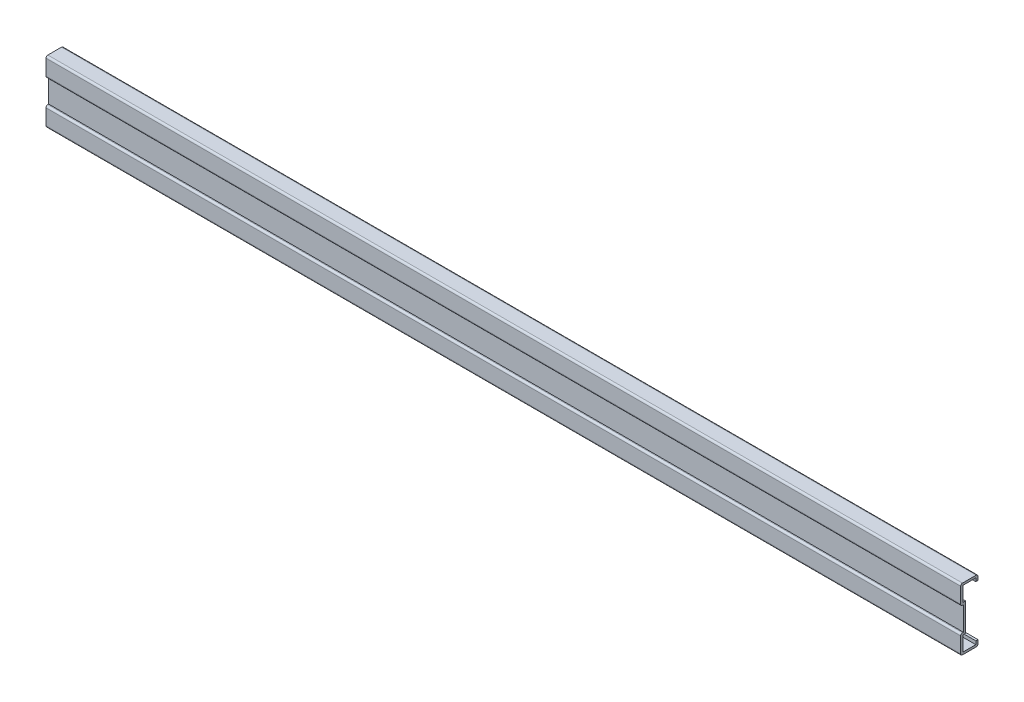
SolidWorks part; units mm, degrees
ref_plane "Спереди" through (0, 0, 0) normal (0, 0, 1) x (1, 0, 0)
ref_plane "Сверху" through (0, 0, 0) normal (0, 1, 0) x (1, 0, 0)
ref_plane "Справа" through (0, 0, 0) normal (1, 0, 0) x (0, 0, -1)
sketch "Эскиз1" plane through (0, 0, 0) normal (1, 0, 0) x (0, 0, -1)
  line L0 (0, 6.5) -> (0, -6.5)
  line L1 (-12.4481, 0) -> (26.4522, 0) construction
  line L2 (0, -6.5) -> (-0.5, -6.5)
  line L3 (-1.5, -7.5) -> (-1.5, -16)
  line L4 (-0.5, -17) -> (7, -17)
  line L5 (8, -16) -> (8, -14)
  line L6 (8, 16) -> (8, 14)
  line L7 (-0.5, 17) -> (7, 17)
  line L8 (-1.5, 7.5) -> (-1.5, 16)
  line L9 (0, 6.5) -> (-0.5, 6.5)
  arc A0 (7, -17) -> (8, -16) centre (7, -16) ccw
  arc A1 (-1.5, -7.5) -> (-0.5, -6.5) centre (-0.5, -7.5) cw
  arc A2 (-1.5, 16) -> (-0.5, 17) centre (-0.5, 16) cw
  arc A3 (-1.5, -16) -> (-0.5, -17) centre (-0.5, -16) ccw
  arc A4 (-1.5, 7.5) -> (-0.5, 6.5) centre (-0.5, 7.5) ccw
  arc A5 (7, 17) -> (8, 16) centre (7, 16) cw
  point P14 (0, 0)
  point P16 (8, -17)
  point P20 (0, 0)
  point P26 (-1.5, -17)
  point P30 (0, 0)
  dimension "D1" = 1
  dimension "D2" = 1
extrude "Вытянуть-Тонкостенный3" add sketch "Эскиз1" along normal blind 500 thin thin type one direction wall 1.2
